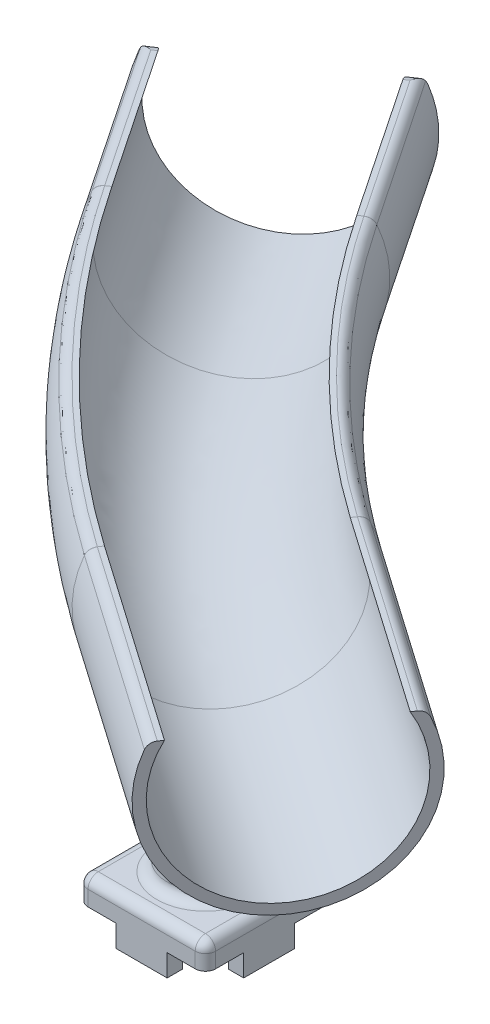
SolidWorks part; units mm, degrees
ref_plane "Front Plane" through (0, 0, 0) normal (0, 0, 1) x (1, 0, 0)
ref_plane "Top Plane" through (0, 0, 0) normal (0, 1, 0) x (1, 0, 0)
ref_plane "Right Plane" through (0, 0, 0) normal (1, 0, 0) x (0, 0, -1)
sketch "Sketch1" plane through (0, 0, 0) normal (0, 0, 1) x (1, 0, 0)
  line L0 (0, 0) -> (0, 30) construction
  dimension "D1" = 30
ref_plane "Plane1" through (0, 0, 0) normal (0.5519, 0, 0.8339) x (0, 1, 0)
ref_plane "Plane2" through (0, 0, 249) normal (0, 0, 1) x (1, 0, 0)
ref_plane "Plane3" through (182.5, 0, 0) normal (1, 0, 0) x (0, 0, -1)
ref_plane "Plane4" through (0, -8.33, 0) normal (0, 1, 0) x (1, 0, 0)
ref_point "Point2"
ref_point "Point4"
ref_point "Point6"
sketch "Sketch2" plane through (0, 0, 249) normal (0, 0, 1) x (1, 0, 0)
  point P0 (0, -4.165)
  dimension "D1" = 4.165
ref_plane "Plane5" through (0, 0, 0) normal (0.0228, 0.9996, 0.0167) x (0.9997, -0.0228, -0.0004)
sketch "Sketch4" plane through (0, 0, 0) normal (0.5519, 0, 0.8339) x (0, 1, 0)
  line L0 (0, 10.8002) -> (0, -22.3315) construction
sketch "Sketch5" plane through (0, 0, 0) normal (0.0228, 0.9996, 0.0167) x (0.9997, -0.0228, -0.0004)
  line L0 (-9.006, -5.9602) -> (18.6218, 12.3239) construction
  line L1 (-9.006, -5.9602) -> (18.6218, 12.3239) construction
  line L2 (0, 0) -> (25.4518, -38.4586)
  line L3 (182.5475, -249.1045) -> (182.5475, -164.1045) construction
  line L4 (78.954, -92.9063) -> (116.5258, -118.7288)
  line L5 (116.5258, -118.7288) -> (182.5475, -164.1045) construction
  arc A0 (78.954, -92.9063) -> (25.4518, -38.4586) centre (192.2357, 71.9187) cw
  point P8 (116.5258, -118.7288)
  point P13 (46.9103, -70.8831)
  dimension "D5" = 200
  dimension "D1" = 85
  dimension "D2" = 85
  dimension "D3" = 84.472
  dimension "D4" = 80.1113
ref_plane "Plane6" through (0, -63.13, 0) normal (0, 1, 0) x (1, 0, 0)
sketch "Sketch7" plane through (0, 0, 0) normal (0.5519, 0, 0.8339) x (0, 1, 0)
  line L0 (30, -19.5959) -> (30, -17.3205)
  line L1 (30, 17.3205) -> (30, 19.5959)
  arc A0 (30, 17.3205) -> (30, -17.3205) centre (20, 0) ccw
  arc A1 (30, 19.5959) -> (30, -19.5959) centre (20, 0) ccw
  point P6 (0, 0)
  dimension "D1" = 20
  dimension "D2" = 22
  dimension "D3" = 30
sweep "Sweep1" add profiles "Sketch7" path "Sketch5"
sketch "Sketch8" plane through (0, -63.13, 0) normal (0, 1, 0) x (1, 0, 0)
  line L1 (37.0679, -80.7299) -> (62.0679, -80.7299)
  line L2 (37.0679, -80.7299) -> (37.0679, -55.7299)
  line L3 (37.0679, -55.7299) -> (62.0679, -55.7299)
  line L4 (62.0679, -80.7299) -> (62.0679, -55.7299)
  line L5 (37.0679, -80.7299) -> (62.0679, -55.7299) construction
  line L6 (37.0679, -55.7299) -> (62.0679, -80.7299) construction
  ellipse E0 centre (192.1857, 71.9819) end of major axis (310.4163, 233.2938) minor radius 199.92 (25.4452, -38.4435) -> (78.9335, -92.8632) ccw construction
  point P8 (49.5679, -68.2299)
  point P13 (49.5679, -68.2299)
  dimension "D1" = 25
  dimension "D2" = 25
extrude "Boss-Extrude1" add sketch "Sketch8" along normal blind 5 separate body
sketch "Sketch9" plane through (0, -58.13, 0) normal (0, 1, 0) x (1, 0, 0)
  circle A0 centre (49.5679, -68.2299) radius 7.5
  circle A1 centre (49.5679, -68.2299) radius 5.5
  ellipse E0 centre (192.1857, 71.9819) end of major axis (310.4163, 233.2938) minor radius 199.92 (25.4452, -38.4435) -> (78.9335, -92.8632) ccw construction
  point P9 (49.5679, -68.2299)
  dimension "D2" = 15
  dimension "D1" = 2
extrude "Boss-Extrude2" add sketch "Sketch9" along normal up to surface (54.3365 mm away) up to face at (50.8395, 11.7189, 67.0068)
sketch "Sketch10" plane through (0, -63.13, 0) normal (0, -1, 0) x (1, 0, 0)
  line L1 (62.0679, 73.2299) -> (59.0679, 73.2299)
  line L2 (62.0679, 73.2299) -> (62.0679, 63.2299)
  line L3 (62.0679, 63.2299) -> (59.0679, 63.2299)
  line L4 (62.0679, 55.7299) -> (62.0679, 80.7299)
  line L5 (62.0679, 80.7299) -> (37.0679, 80.7299)
  line L6 (37.0679, 80.7299) -> (37.0679, 55.7299)
  line L7 (37.0679, 55.7299) -> (62.0679, 55.7299)
  line L8 (62.0679, 55.7299) -> (62.0679, 80.7299) construction
  line L9 (62.0679, 80.7299) -> (37.0679, 80.7299) construction
  line L10 (37.0679, 80.7299) -> (37.0679, 55.7299) construction
  line L11 (37.0679, 55.7299) -> (62.0679, 55.7299) construction
  line L12 (59.0679, 73.2299) -> (59.0679, 63.2299)
  line L13 (37.0679, 73.2299) -> (40.0679, 73.2299)
  line L14 (37.0679, 73.2299) -> (37.0679, 63.2299)
  line L15 (37.0679, 63.2299) -> (40.0679, 63.2299)
  line L16 (40.0679, 73.2299) -> (40.0679, 63.2299)
  line L17 (44.5679, 55.7299) -> (54.5679, 55.7299)
  line L18 (44.5679, 55.7299) -> (44.5679, 58.7299)
  line L19 (44.5679, 58.7299) -> (54.5679, 58.7299)
  line L20 (54.5679, 55.7299) -> (54.5679, 58.7299)
  line L21 (54.5679, 80.7299) -> (44.5679, 80.7299)
  line L22 (54.5679, 80.7299) -> (54.5679, 77.7299)
  line L23 (54.5679, 77.7299) -> (44.5679, 77.7299)
  line L24 (44.5679, 80.7299) -> (44.5679, 77.7299)
  point P20 (49.5679, 58.7299)
  point P21 (49.5679, 80.7299)
  point P22 (49.5679, 77.7299)
  point P23 (59.0679, 68.2299)
  point P24 (40.0679, 68.2299)
  point P25 (62.0679, 68.2299)
  dimension "D2" = 10
  dimension "D3" = 3
  dimension "D1" = 0
extrude "Boss-Extrude3" add sketch "Sketch10" along normal blind 4.3
sketch "Sketch11" plane through (0, 0, 0) normal (-0.5519, 0, -0.8339) x (-0.8339, 0, 0.5519)
  line L1 (-26.8269, 34.3434) -> (26.8269, 34.3434)
  line L2 (-26.8269, 34.3434) -> (-26.8269, -9.8466)
  line L3 (-26.8269, -9.8466) -> (26.8269, -9.8466)
  line L4 (26.8269, 34.3434) -> (26.8269, -9.8466)
  line L5 (-26.8269, 34.3434) -> (26.8269, -9.8466) construction
  line L6 (-26.8269, -9.8466) -> (26.8269, 34.3434) construction
  point P0 (0, 12.2484)
extrude "Cut-Extrude1" cut sketch "Sketch11" against normal blind 12
fillet "Fillet1" radius 2 18 edges at (49.5679, -58.13, 80.7299) (37.0679, -58.13, 68.2299) (49.5679, -58.13, 55.7299) (62.0679, -58.13, 68.2299) (48.4903, -3.5891, 75.6521) (49.5679, -58.13, 75.7299) (37.0679, -60.63, 80.7299) (37.0679, -60.63, 55.7299) (62.0679, -60.63, 55.7299) (62.0679, -60.63, 80.7299) (22.0153, 29.6815, -0.1811) (-8.7688, 29.6815, 20.1944) (-0.3065, 29.2289, 35.0408) (63.4624, 27.8298, 54.636) (32.375, 29.2289, 13.4094) (35.5078, 27.6243, 82.1041) (86.4761, 25.7903, 122.2059) (108.6766, 26.2079, 89.9109)
